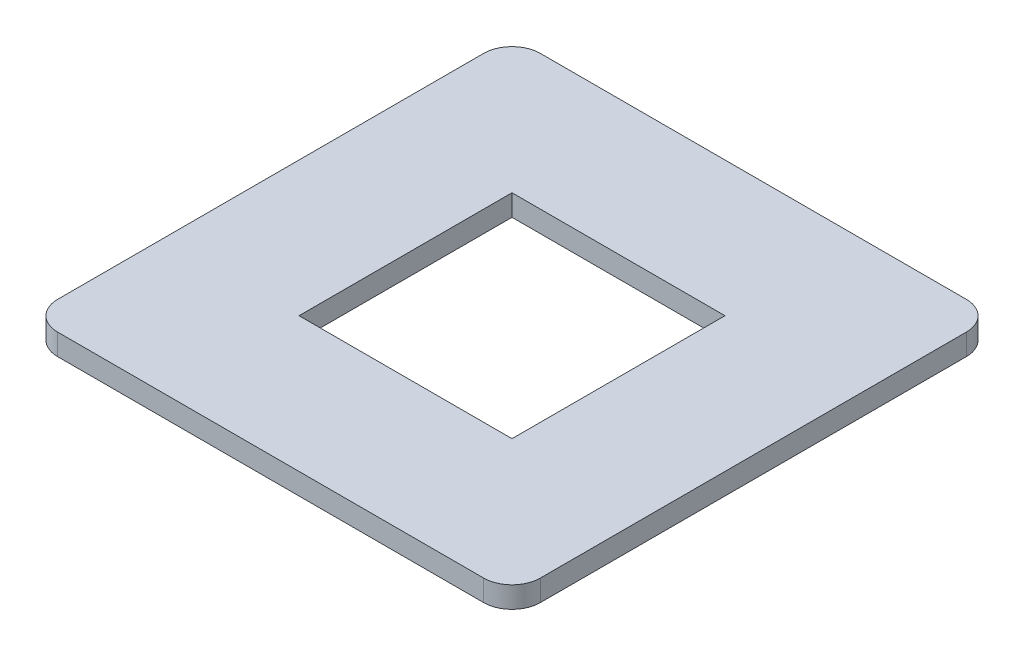
SolidWorks part; units mm, degrees
ref_plane "Front Plane" through (0, 0, 0) normal (0, 0, 1) x (1, 0, 0)
ref_plane "Top Plane" through (0, 0, 0) normal (0, 1, 0) x (1, 0, 0)
ref_plane "Right Plane" through (0, 0, 0) normal (1, 0, 0) x (0, 0, -1)
sketch "Sketch2" plane through (0, 0, 0) normal (0, 1, 0) x (1, 0, 0)
  line L1 (-85, -85) -> (85, -85)
  line L2 (-85, -85) -> (-85, 85)
  line L3 (-85, 85) -> (85, 85)
  line L4 (85, -85) -> (85, 85)
  line L5 (-85, -85) -> (85, 85) construction
  line L6 (-85, 85) -> (85, -85) construction
  point P0 (0, 0)
  dimension "D1" = 170
  dimension "D2" = 170
extrude "Base" add sketch "Sketch2" along normal blind 7.5
sketch "Sketch3" plane through (0, 7.5, 0) normal (0, 1, 0) x (1, 0, 0)
  line L1 (-37.5, -37.5) -> (37.5, -37.5)
  line L2 (-37.5, -37.5) -> (-37.5, 37.5)
  line L3 (-37.5, 37.5) -> (37.5, 37.5)
  line L4 (37.5, -37.5) -> (37.5, 37.5)
  line L5 (-37.5, -37.5) -> (37.5, 37.5) construction
  line L6 (-37.5, 37.5) -> (37.5, -37.5) construction
  point P0 (0, 0)
  dimension "D1" = 75
  dimension "D2" = 75
extrude "Hole" cut sketch "Sketch3" against normal up to surface (7.5 mm away) up to face at (0, 0, 0)
fillet "Fillet1" radius 10 4 edges at (-85, 3.75, -85) (-85, 3.75, 85) (85, 3.75, -85) (85, 3.75, 85)
